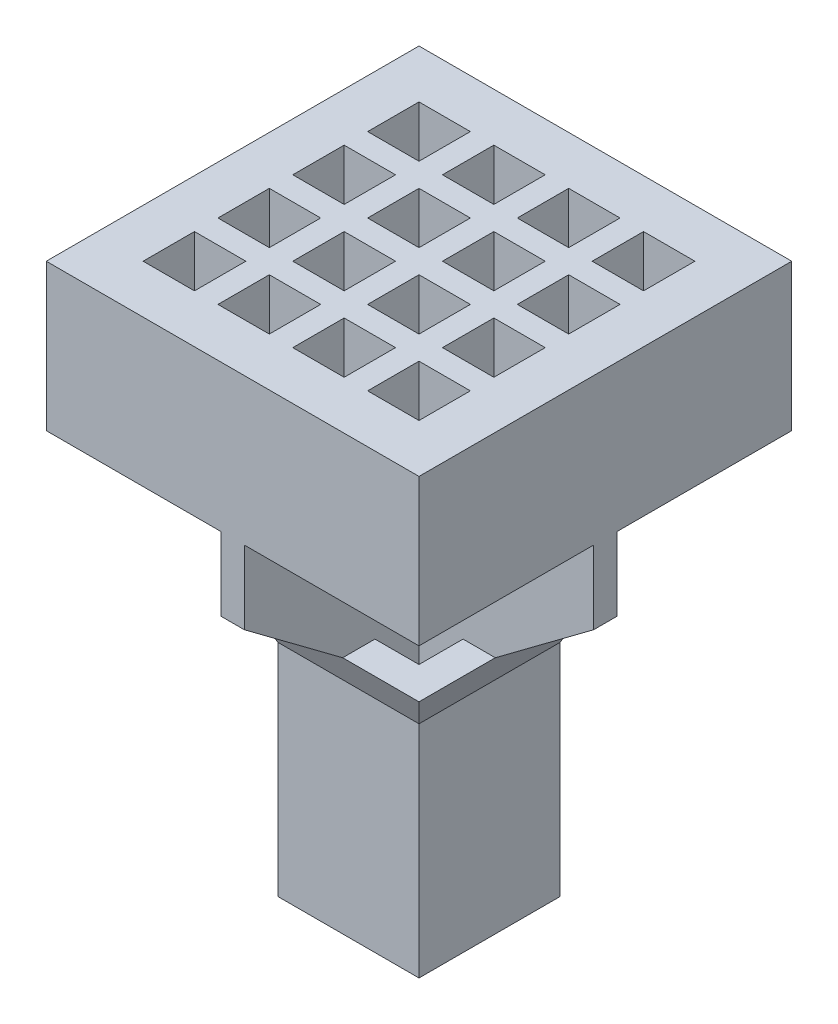
SolidWorks part; units mm, degrees
note: The reader was unsure of these and kept them because the rebuilt part matched: shared geometry of "Sketch7<3>", "Sketch9<2>".
ref_plane "Front Plane" through (0, 0, 0) normal (0, 0, 1) x (1, 0, 0)
ref_plane "Top Plane" through (0, 0, 0) normal (0, 1, 0) x (1, 0, 0)
ref_plane "Right Plane" through (0, 0, 0) normal (1, 0, 0) x (0, 0, -1)
sketch "top_panel" plane through (0, 0, 0) normal (0, 1, 0) x (1, 0, 0)
  line L1 (-18.4144, 13.6444) -> (-15.8744, 13.6444)
  line L2 (-18.4144, 13.6444) -> (-18.4144, 11.1044)
  line L3 (-18.4144, 11.1044) -> (-15.8744, 11.1044)
  line L4 (-15.8744, 13.6444) -> (-15.8744, 11.1044)
  dimension "D1" = 2.54
  dimension "D2" = 2.54
extrude "Boss-Extrude1" add sketch "top_panel" against normal blind 1
sketch "well_holes" plane through (0, 0, 0) normal (0, 1, 0) x (1, 0, 0)
  line L0 (-17.5744, 13.3144) -> (-17.2244, 13.3144)
  line L1 (-18.0844, 13.3144) -> (-17.7344, 13.3144)
  line L2 (-18.0844, 13.3144) -> (-18.0844, 12.9644)
  line L3 (-18.0844, 12.9644) -> (-17.7344, 12.9644)
  line L4 (-17.7344, 13.3144) -> (-17.7344, 12.9644)
  line L5 (-17.2244, 13.3144) -> (-17.2244, 12.9644)
  line L6 (-17.5744, 12.9644) -> (-17.2244, 12.9644)
  line L7 (-17.5744, 13.3144) -> (-17.5744, 12.9644)
  line L8 (-17.0644, 13.3144) -> (-16.7144, 13.3144)
  line L9 (-16.7144, 13.3144) -> (-16.7144, 12.9644)
  line L10 (-17.0644, 12.9644) -> (-16.7144, 12.9644)
  line L11 (-17.0644, 13.3144) -> (-17.0644, 12.9644)
  line L12 (-16.5544, 13.3144) -> (-16.2044, 13.3144)
  line L13 (-16.2044, 13.3144) -> (-16.2044, 12.9644)
  line L14 (-16.5544, 12.9644) -> (-16.2044, 12.9644)
  line L15 (-16.5544, 13.3144) -> (-16.5544, 12.9644)
  line L16 (-17.5744, 12.8044) -> (-17.2244, 12.8044)
  line L17 (-17.2244, 12.8044) -> (-17.2244, 12.4544)
  line L18 (-17.5744, 12.4544) -> (-17.2244, 12.4544)
  line L19 (-17.5744, 12.8044) -> (-17.5744, 12.4544)
  line L20 (-17.0644, 12.8044) -> (-16.7144, 12.8044)
  line L21 (-16.7144, 12.8044) -> (-16.7144, 12.4544)
  line L22 (-17.0644, 12.4544) -> (-16.7144, 12.4544)
  line L23 (-17.0644, 12.8044) -> (-17.0644, 12.4544)
  line L24 (-16.5544, 12.8044) -> (-16.2044, 12.8044)
  line L25 (-16.2044, 12.8044) -> (-16.2044, 12.4544)
  line L26 (-16.5544, 12.4544) -> (-16.2044, 12.4544)
  line L27 (-16.5544, 12.8044) -> (-16.5544, 12.4544)
  line L28 (-17.5744, 12.2944) -> (-17.2244, 12.2944)
  line L29 (-17.2244, 12.2944) -> (-17.2244, 11.9444)
  line L30 (-17.5744, 11.9444) -> (-17.2244, 11.9444)
  line L31 (-17.5744, 12.2944) -> (-17.5744, 11.9444)
  line L32 (-17.0644, 12.2944) -> (-16.7144, 12.2944)
  line L33 (-16.7144, 12.2944) -> (-16.7144, 11.9444)
  line L34 (-17.0644, 11.9444) -> (-16.7144, 11.9444)
  line L35 (-17.0644, 12.2944) -> (-17.0644, 11.9444)
  line L36 (-16.5544, 12.2944) -> (-16.2044, 12.2944)
  line L37 (-16.2044, 12.2944) -> (-16.2044, 11.9444)
  line L38 (-16.5544, 11.9444) -> (-16.2044, 11.9444)
  line L39 (-16.5544, 12.2944) -> (-16.5544, 11.9444)
  line L40 (-17.5744, 11.7844) -> (-17.2244, 11.7844)
  line L41 (-17.2244, 11.7844) -> (-17.2244, 11.4344)
  line L42 (-17.5744, 11.4344) -> (-17.2244, 11.4344)
  line L43 (-17.5744, 11.7844) -> (-17.5744, 11.4344)
  line L44 (-17.0644, 11.7844) -> (-16.7144, 11.7844)
  line L45 (-16.7144, 11.7844) -> (-16.7144, 11.4344)
  line L46 (-17.0644, 11.4344) -> (-16.7144, 11.4344)
  line L47 (-17.0644, 11.7844) -> (-17.0644, 11.4344)
  line L48 (-16.5544, 11.7844) -> (-16.2044, 11.7844)
  line L49 (-16.2044, 11.7844) -> (-16.2044, 11.4344)
  line L50 (-16.5544, 11.4344) -> (-16.2044, 11.4344)
  line L51 (-16.5544, 11.7844) -> (-16.5544, 11.4344)
  line L52 (-18.0844, 12.8044) -> (-17.7344, 12.8044)
  line L53 (-17.7344, 12.8044) -> (-17.7344, 12.4544)
  line L54 (-18.0844, 12.4544) -> (-17.7344, 12.4544)
  line L55 (-18.0844, 12.8044) -> (-18.0844, 12.4544)
  line L56 (-18.0844, 12.2944) -> (-17.7344, 12.2944)
  line L57 (-17.7344, 12.2944) -> (-17.7344, 11.9444)
  line L58 (-18.0844, 11.9444) -> (-17.7344, 11.9444)
  line L59 (-18.0844, 12.2944) -> (-18.0844, 11.9444)
  line L60 (-18.0844, 11.7844) -> (-17.7344, 11.7844)
  line L61 (-17.7344, 11.7844) -> (-17.7344, 11.4344)
  line L62 (-18.0844, 11.4344) -> (-17.7344, 11.4344)
  line L63 (-18.0844, 11.7844) -> (-18.0844, 11.4344)
  line L64 (-18.4144, 13.6444) -> (-18.4144, 11.1044) construction
  line L65 (-15.8744, 13.6444) -> (-18.4144, 13.6444) construction
  dimension "D1" = 0.35
  dimension "D2" = 0.35
  dimension "D5" = 0.33
  dimension "D6" = 0.33
  dimension "D3" = 4
  dimension "D4" = 4
extrude "wells" cut sketch "well_holes" against normal blind 1
sketch "support_wall_sketch" plane through (0, -1, 0) normal (0, -1, 0) x (-1, 0, 0)
  line L6 (18.4144, 11.1044) -> (15.8744, 11.1044) construction
  line L7 (17.0644, 11.1044) -> (17.2244, 11.1044)
  line L8 (17.0644, 11.1044) -> (17.0644, 13.6444)
  line L9 (17.0644, 13.6444) -> (17.2244, 13.6444)
  line L10 (17.2244, 11.1044) -> (17.2244, 13.6444)
  line L11 (15.8744, 13.6444) -> (18.4144, 13.6444) construction
ref_plane "Plane1" through (0, -2, 0) normal (0, 1, 0) x (1, 0, 0)
sketch "Sketch4" plane through (0, -2, 0) normal (0, 1, 0) x (1, 0, 0)
  line L1 (-17.7444, 12.2944) -> (-16.5444, 12.2944)
  line L2 (-17.7444, 12.2944) -> (-17.7444, 12.4544)
  line L3 (-17.7444, 12.4544) -> (-16.5444, 12.4544)
  line L4 (-16.5444, 12.2944) -> (-16.5444, 12.4544)
  line L10 (-16.7144, 12.4544) -> (-16.7144, 12.8044) construction
  line L11 (-17.5744, 12.8044) -> (-17.5744, 12.4544) construction
  dimension "D1" = 0.17
  dimension "D2" = 0.17
sketch "Sketch5" plane through (0, -1, 0) normal (0, -1, 0) x (-1, 0, 0)
  line L0 (18.4144, 13.6444) -> (18.4144, 11.1044) construction
  line L1 (18.4144, 12.2944) -> (15.8744, 12.2944)
  line L2 (18.4144, 12.2944) -> (18.4144, 12.4544)
  line L3 (18.4144, 12.4544) -> (15.8744, 12.4544)
  line L4 (15.8744, 12.2944) -> (15.8744, 12.4544)
  line L5 (15.8744, 11.1044) -> (15.8744, 13.6444) construction
sketch "Sketch6" plane through (0, -2, 0) normal (0, 1, 0) x (1, 0, 0)
  line L1 (-17.2244, 11.9444) -> (-17.0644, 11.9444)
  line L2 (-17.2244, 11.9444) -> (-17.2244, 12.8044)
  line L3 (-17.2244, 12.8044) -> (-17.0644, 12.8044)
  line L4 (-17.0644, 11.9444) -> (-17.0644, 12.8044)
extrude "Boss-Extrude5" add sketch "Sketch5" along normal blind 0.5
loft "Loft3" add profiles "Sketch4" section face at (-17.1444, -1.5, -12.3744) section "Sketch4" connector at (-18.4144, -1.5, -12.2944) connector at (-17.7444, -2, -12.2944)
extrude "Boss-Extrude7" add sketch "support_wall_sketch" along normal blind 0.5
sketch "Sketch7" plane through (0, -2, 0) normal (0, 1, 0) x (1, 0, 0)
  line L1 (-17.0644, 12.9744) -> (-17.2244, 12.9744)
  line L2 (-17.0644, 12.9744) -> (-17.0644, 12.4544)
  line L3 (-17.0644, 12.4544) -> (-17.2244, 12.4544)
  line L4 (-17.2244, 12.9744) -> (-17.2244, 12.4544)
  line L5 (-17.0644, 11.7744) -> (-17.2244, 11.7744)
  line L6 (-17.0644, 11.7744) -> (-17.0644, 12.2944)
  line L7 (-17.0644, 12.2944) -> (-17.2244, 12.2944)
  line L8 (-17.2244, 11.7744) -> (-17.2244, 12.2944)
  dimension "D1" = 0.52
  dimension "D2" = 0.52
loft "Loft6" add section face at (-17.1444, -1.5, -11.6994) section "Sketch7" connector at (-17.0644, -1.5, -11.1044) connector at (-17.0644, -2, -11.7744)
loft "Loft7" add section face at (-17.1444, -1.5, -13.0494) section "Sketch7<3>" connector at (-17.2244, -1.5, -13.6444) connector at (-17.2244, -2, -12.9744)
sketch "Sketch7<3>" plane through (0, -2, 0) normal (0, 1, 0) x (1, 0, 0) same geometry as "Sketch7"
sketch "Sketch8" plane through (0, -2, 0) normal (0, 1, 0) x (1, 0, 0)
  line L1 (-17.7444, 11.7744) -> (-16.5444, 11.7744)
  line L2 (-17.7444, 11.7744) -> (-17.7444, 12.9744)
  line L3 (-17.7444, 12.9744) -> (-16.5444, 12.9744)
  line L4 (-16.5444, 11.7744) -> (-16.5444, 12.9744)
  line L5 (-17.0644, 12.2944) -> (-16.5444, 12.2944) construction
  line L6 (-16.5444, 12.4544) -> (-17.0644, 12.4544) construction
  line L7 (-17.0644, 11.7744) -> (-17.0644, 12.2944) construction
  dimension "D1" = 1.2
  dimension "D2" = 0.52
  dimension "D3" = 0.52
  dimension "D4" = 0.52
  dimension "D5" = 0.52
ref_plane "Plane2" through (0, -2.25, 0) normal (0, 1, 0) x (1, 0, 0)
sketch "Sketch9" plane through (0, -2.25, 0) normal (0, 1, 0) x (1, 0, 0)
  line L0 (-17.2244, 11.7744) -> (-17.2244, 12.2944) construction
  line L1 (-17.6244, 11.8944) -> (-16.6644, 11.8944)
  line L2 (-17.6244, 11.8944) -> (-17.6244, 12.8544)
  line L3 (-17.6244, 12.8544) -> (-16.6644, 12.8544)
  line L4 (-16.6644, 11.8944) -> (-16.6644, 12.8544)
  line L5 (-17.0644, 11.7744) -> (-17.0644, 12.2944) construction
  line L6 (-17.0644, 12.2944) -> (-16.5444, 12.2944) construction
  dimension "D1" = 0.96
  dimension "D2" = 0.96
  dimension "D3" = 0.4
  dimension "D4" = 0.4
  dimension "D5" = 0.4
loft "Loft8" add profiles "Sketch8", "Sketch9" connector at (-17.7444, -2, -11.7744) connector at (-17.6244, -2.25, -11.8944)
sketch "tetrode_entry_holdes" plane through (0, -2, 0) normal (0, 1, 0) x (1, 0, 0)
  line L1 (-17.2244, 12.2944) -> (-17.5244, 12.2944)
  line L2 (-17.2244, 12.2944) -> (-17.2244, 11.9944)
  line L3 (-17.2244, 11.9944) -> (-17.5244, 11.9944)
  line L4 (-17.5244, 12.2944) -> (-17.5244, 11.9944)
  line L5 (-16.7644, 11.9944) -> (-17.0644, 11.9944)
  line L6 (-16.7644, 12.2944) -> (-16.7644, 11.9944)
  line L7 (-16.7644, 12.2944) -> (-17.0644, 12.2944)
  line L8 (-17.0644, 12.2944) -> (-17.0644, 11.9944)
  line L9 (-16.7644, 12.4544) -> (-17.0644, 12.4544)
  line L10 (-16.7644, 12.7544) -> (-16.7644, 12.4544)
  line L11 (-16.7644, 12.7544) -> (-17.0644, 12.7544)
  line L12 (-17.0644, 12.7544) -> (-17.0644, 12.4544)
  line L13 (-17.2244, 12.4544) -> (-17.5244, 12.4544)
  line L14 (-17.2244, 12.7544) -> (-17.2244, 12.4544)
  line L15 (-17.2244, 12.7544) -> (-17.5244, 12.7544)
  line L16 (-17.5244, 12.7544) -> (-17.5244, 12.4544)
  dimension "D1" = 0.3
  dimension "D2" = 0.3
  dimension "D3" = 2
  dimension "D4" = 2
extrude "Boss-Extrude8" add sketch "Sketch9<2>" against normal blind 1.5
sketch "Sketch9<2>" plane through (0, -2.25, 0) normal (0, 1, 0) x (1, 0, 0) same geometry as "Sketch9"
extrude "Cut-Extrude1" cut sketch "tetrode_entry_holdes" against normal blind 1.75
